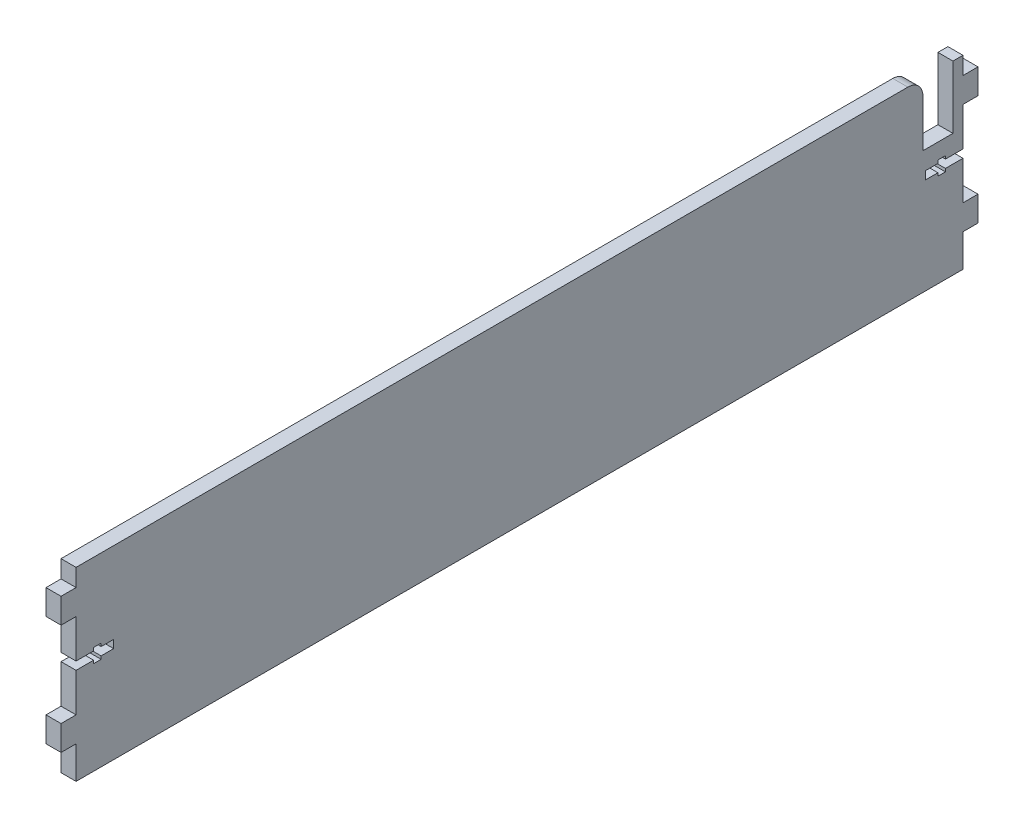
SolidWorks part; units mm, degrees
ref_plane "Front Plane" through (0, 0, 0) normal (0, 0, 1) x (1, 0, 0)
ref_plane "Top Plane" through (0, 0, 0) normal (0, 1, 0) x (1, 0, 0)
ref_plane "Right Plane" through (0, 0, 0) normal (1, 0, 0) x (0, 0, -1)
sketch "Sketch1" plane through (0, 0, 0) normal (1, 0, 0) x (0, 0, -1)
  line L1 (-177, -40) -> (177, -40)
  line L2 (-177, -40) -> (-177, 40)
  line L3 (-177, 40) -> (177, 40)
  line L4 (177, -40) -> (177, 40)
  line L5 (-177, -40) -> (177, 40) construction
  line L6 (-177, 40) -> (177, -40) construction
  point P0 (0, 0)
  dimension "D1" = 80
  dimension "D2" = 354
extrude "Boss-Extrude1" add sketch "Sketch1" along normal blind 6
sketch "Sketch3" plane through (0, 40, 0) normal (0, 1, 0) x (1, 0, 0)
  line L0 (-213.5, -147) -> (219.5, -147) construction
  line L1 (-213.5, 323) -> (-213.5, 177) construction
  line L2 (219.5, 323) -> (219.5, 177) construction
  line L3 (244.3, -177) -> (-238.3, -177) construction
  line L5 (0, -147) -> (6, -147)
  line L6 (0, -147) -> (0, -141)
  line L7 (0, -141) -> (6, -141)
  line L8 (6, -147) -> (6, -141)
  line L10 (6, -135) -> (6, -129)
  line L11 (0, -129) -> (6, -129)
  line L12 (0, -135) -> (0, -129)
  line L13 (0, -135) -> (6, -135)
  line L14 (6, -123) -> (6, -117)
  line L15 (0, -117) -> (6, -117)
  line L16 (0, -123) -> (0, -117)
  line L17 (0, -123) -> (6, -123)
  line L18 (6, -111) -> (6, -105)
  line L19 (0, -105) -> (6, -105)
  line L20 (0, -111) -> (0, -105)
  line L21 (0, -111) -> (6, -111)
  line L22 (6, -99) -> (6, -93)
  line L23 (0, -93) -> (6, -93)
  line L24 (0, -99) -> (0, -93)
  line L25 (0, -99) -> (6, -99)
  line L26 (6, -87) -> (6, -81)
  line L27 (0, -81) -> (6, -81)
  line L28 (0, -87) -> (0, -81)
  line L29 (0, -87) -> (6, -87)
  line L30 (6, -75) -> (6, -69)
  line L31 (0, -69) -> (6, -69)
  line L32 (0, -75) -> (0, -69)
  line L33 (0, -75) -> (6, -75)
  line L34 (6, -63) -> (6, -57)
  line L35 (0, -57) -> (6, -57)
  line L36 (0, -63) -> (0, -57)
  line L37 (0, -63) -> (6, -63)
  line L38 (6, -51) -> (6, -45)
  line L39 (0, -45) -> (6, -45)
  line L40 (0, -51) -> (0, -45)
  line L41 (0, -51) -> (6, -51)
  line L42 (6, -39) -> (6, -33)
  line L43 (0, -33) -> (6, -33)
  line L44 (0, -39) -> (0, -33)
  line L45 (0, -39) -> (6, -39)
  line L46 (6, -27) -> (6, -21)
  line L47 (0, -21) -> (6, -21)
  line L48 (0, -27) -> (0, -21)
  line L49 (0, -27) -> (6, -27)
  line L50 (6, -15) -> (6, -9)
  line L51 (0, -9) -> (6, -9)
  line L52 (0, -15) -> (0, -9)
  line L53 (0, -15) -> (6, -15)
  line L54 (6, -3) -> (6, 3)
  line L55 (0, 3) -> (6, 3)
  line L56 (0, -3) -> (0, 3)
  line L57 (0, -3) -> (6, -3)
  line L58 (6, 9) -> (6, 15)
  line L59 (0, 15) -> (6, 15)
  line L60 (0, 9) -> (0, 15)
  line L61 (0, 9) -> (6, 9)
  line L62 (6, 21) -> (6, 27)
  line L63 (0, 27) -> (6, 27)
  line L64 (0, 21) -> (0, 27)
  line L65 (0, 21) -> (6, 21)
  line L66 (6, 33) -> (6, 39)
  line L67 (0, 39) -> (6, 39)
  line L68 (0, 33) -> (0, 39)
  line L69 (0, 33) -> (6, 33)
  line L70 (6, 45) -> (6, 51)
  line L71 (0, 51) -> (6, 51)
  line L72 (0, 45) -> (0, 51)
  line L73 (0, 45) -> (6, 45)
  line L74 (6, 57) -> (6, 63)
  line L75 (0, 63) -> (6, 63)
  line L76 (0, 57) -> (0, 63)
  line L77 (0, 57) -> (6, 57)
  line L78 (6, 69) -> (6, 75)
  line L79 (0, 75) -> (6, 75)
  line L80 (0, 69) -> (0, 75)
  line L81 (0, 69) -> (6, 69)
  line L82 (6, 81) -> (6, 87)
  line L83 (0, 87) -> (6, 87)
  line L84 (0, 81) -> (0, 87)
  line L85 (0, 81) -> (6, 81)
  line L86 (6, 93) -> (6, 99)
  line L87 (0, 99) -> (6, 99)
  line L88 (0, 93) -> (0, 99)
  line L89 (0, 93) -> (6, 93)
  line L90 (6, 105) -> (6, 111)
  line L91 (0, 111) -> (6, 111)
  line L92 (0, 105) -> (0, 111)
  line L93 (0, 105) -> (6, 105)
  line L94 (6, 117) -> (6, 123)
  line L95 (0, 123) -> (6, 123)
  line L96 (0, 117) -> (0, 123)
  line L97 (0, 117) -> (6, 117)
  line L98 (6, 129) -> (6, 135)
  line L99 (0, 135) -> (6, 135)
  line L100 (0, 129) -> (0, 135)
  line L101 (0, 129) -> (6, 129)
  line L102 (6, 141) -> (6, 147)
  line L103 (0, 147) -> (6, 147)
  line L104 (0, 141) -> (0, 147)
  line L105 (0, 141) -> (6, 141)
  line L106 (6, 153) -> (6, 159)
  line L107 (0, 159) -> (6, 159)
  line L108 (0, 153) -> (0, 159)
  line L109 (0, 153) -> (6, 153)
  line L110 (6, 165) -> (6, 171)
  line L111 (0, 171) -> (6, 171)
  line L112 (0, 165) -> (0, 171)
  line L113 (0, 165) -> (6, 165)
  line L114 (0, 177) -> (0, -177) construction
  line L115 (6, 177) -> (6, -177) construction
  dimension "D1" = 30
  dimension "D2" = 6
  dimension "D3" = 27
sketch "Sketch4" plane through (0, 0, 177) normal (0, 0, 1) x (1, 0, 0)
  line L1 (6, 27) -> (0, 27) construction
  line L2 (6, 17) -> (6, 27) construction
  line L3 (0, 27) -> (0, 17) construction
  line L4 (0, 17) -> (6, 17) construction
  line L7 (6, -17) -> (0, -17) construction
  line L8 (6, -27) -> (6, -17) construction
  line L9 (0, -17) -> (0, -27) construction
  line L10 (0, -27) -> (6, -27) construction
  line L13 (6, 27) -> (0, 27)
  line L14 (6, 17) -> (6, 27)
  line L15 (0, 27) -> (0, 17)
  line L16 (0, 17) -> (6, 17)
  line L17 (6, -17) -> (0, -17)
  line L18 (6, -27) -> (6, -17)
  line L19 (0, -17) -> (0, -27)
  line L20 (0, -27) -> (6, -27)
extrude "Boss-Extrude2" add sketch "Sketch4" along normal blind 6
sketch "Sketch5" plane through (0, 0, 0) normal (-1, 0, 0) x (0, 0, 1)
  line L0 (177, 17) -> (177, -17) construction
  line L7 (0, 0) -> (0, -20.5925) construction
  line L8 (-177, 1.6) -> (-170, 1.6)
  line L9 (-167, 2.8) -> (-170, 2.8)
  line L10 (-167, 1.6) -> (-162, 1.6)
  line L11 (-162, -1.6) -> (-162, 1.6)
  line L12 (-167, -1.6) -> (-162, -1.6)
  line L13 (-167, -2.8) -> (-170, -2.8)
  line L14 (-177, -1.6) -> (-170, -1.6)
  line L15 (-170, -2.8) -> (-170, -1.6)
  line L16 (-170, 1.6) -> (-170, 2.8)
  line L17 (-167, 1.6) -> (-167, 2.8)
  line L18 (-167, -2.8) -> (-167, -1.6)
  line L19 (183, -1.6) -> (183, 1.6) construction
  line L20 (183, -1.6) -> (183, 1.6)
  line L21 (183, 0) -> (146.4296, 0) construction
  line L25 (177, -1.6) -> (177, 1.6)
  line L26 (167, -2.8) -> (167, -1.6)
  line L27 (167, 1.6) -> (167, 2.8)
  line L28 (170, 1.6) -> (170, 2.8)
  line L29 (170, -2.8) -> (170, -1.6)
  line L30 (177, -1.6) -> (170, -1.6)
  line L31 (167, -2.8) -> (170, -2.8)
  line L32 (167, -1.6) -> (162, -1.6)
  line L33 (162, -1.6) -> (162, 1.6)
  line L34 (167, 1.6) -> (162, 1.6)
  line L35 (167, 2.8) -> (170, 2.8)
  line L36 (177, 1.6) -> (170, 1.6)
  line L37 (-177, -1.6) -> (-177, 1.6)
  line L38 (-183, -1.6) -> (-183, 1.6)
  point P0 (177, 0)
  dimension "D1" = 15
  dimension "D2" = 5.6
  dimension "D3" = 3.2
  dimension "D4" = 7
  dimension "D5" = 3
extrude "Cut-Extrude3" cut sketch "Sketch5" against normal up to next contours L25 L36 L28 L35 L27 L34 L33 L32 L26 L31 L29 L30 | L37 L14 L15 L13 L18 L12 L11 L10 L17 L9 L16 L8 region at (0, 0, -169.3696) region at (0, 0, 169.3696)
sketch "Sketch7" plane through (0, 0, -177) normal (0, 0, -1) x (-1, 0, 0)
  line L1 (-6, 27) -> (0, 27)
  line L2 (-6, 27) -> (-6, 17)
  line L3 (-6, 17) -> (0, 17)
  line L4 (0, 27) -> (0, 17)
  line L6 (-6, -17) -> (0, -17)
  line L7 (-6, -17) -> (-6, -27)
  line L8 (-6, -27) -> (0, -27)
  line L9 (0, -17) -> (0, -27)
  line L11 (0, 1.6) -> (0, 40) construction
  line L12 (0, 17) -> (-6, 17) construction
  line L13 (-6, 1.6) -> (-6, 40) construction
  line L14 (-6, 27) -> (0, 27) construction
  line L15 (-6, -40) -> (-6, -1.6) construction
  line L16 (0, -40) -> (0, -1.6) construction
  line L17 (-6, -17) -> (0, -17) construction
  line L18 (0, -27) -> (-6, -27) construction
extrude "Boss-Extrude3" add sketch "Sketch7" along normal blind 6
sketch "Sketch8" plane through (0, 40, 0) normal (0, 1, 0) x (1, 0, 0)
  line L1 (0, 177) -> (6, 177)
  line L2 (0, 177) -> (0, -177)
  line L3 (0, -177) -> (6, -177)
  line L4 (6, 177) -> (6, -177)
extrude "Cut-Extrude4" cut sketch "Sketch8" against normal blind 6
sketch "Sketch9" plane through (0, 34, 0) normal (0, 1, 0) x (1, 0, 0)
  line L0 (0, 177) -> (0, -177) construction
  line L1 (0, 173) -> (6, 173)
  line L2 (0, 173) -> (0, 161)
  line L3 (0, 161) -> (6, 161)
  line L4 (6, 173) -> (6, 161)
  line L5 (6, -177) -> (6, 177) construction
  line L6 (329.25, 177) -> (-103.75, 177) construction
  dimension "D1" = 4
  dimension "D2" = 12
extrude "Cut-Extrude5" cut sketch "Sketch9" against normal blind 25
fillet "Fillet1" radius 6 1 edges at (3, 34, -161)
